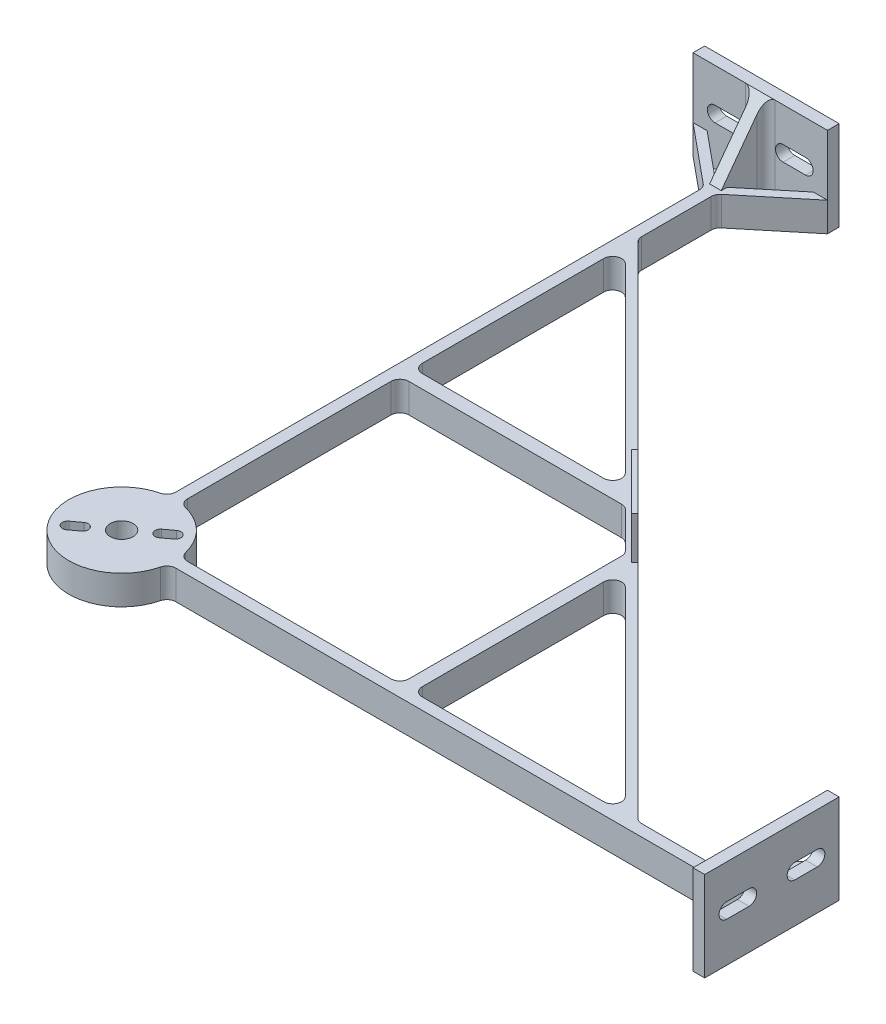
SolidWorks part; units mm, degrees
ref_plane "Front Plane" through (0, 0, 0) normal (0, 0, 1) x (1, 0, 0)
ref_plane "Top Plane" through (0, 0, 0) normal (0, 1, 0) x (1, 0, 0)
ref_plane "Right Plane" through (0, 0, 0) normal (1, 0, 0) x (0, 0, -1)
sketch "Sketch1" plane through (0, 0, 0) normal (0, 1, 0) x (1, 0, 0)
  line L0 (1.651, 14.8948) -> (1.651, 77.2021)
  line L1 (0, 0) -> (0, 189.2633) construction
  line L2 (-1.651, 14.8948) -> (-1.651, 180.975)
  line L3 (-1.651, 180.975) -> (1.651, 180.975)
  line L4 (-16.663, -12.33) -> (16.2408, 12.0176) construction
  line L5 (14.8948, -1.651) -> (180.975, -1.651)
  line L6 (6.3296, 4.6836) -> (8.7797, 6.4967) construction
  line L7 (5.4231, 5.9087) -> (7.8732, 7.7217)
  line L8 (180.975, -1.651) -> (180.975, 1.651)
  line L9 (14.8948, 1.651) -> (141.0789, 1.651)
  line L10 (7.2361, 3.4586) -> (9.6862, 5.2716)
  line L11 (0, 0) -> (12.0155, -16.238) construction
  line L12 (-6.3296, -4.6836) -> (-8.7797, -6.4967) construction
  line L13 (-7.2361, -3.4586) -> (-9.6862, -5.2716)
  line L14 (-5.4231, -5.9087) -> (-7.8732, -7.7217)
  line L15 (-1.651, 14.8948) -> (14.8948, -1.651) construction
  line L16 (1.651, 141.0789) -> (61.7178, 81.0121)
  line L17 (144.6711, 1.651) -> (1.651, 144.6711)
  line L18 (144.6711, 1.651) -> (166.629, 1.651)
  line L19 (141.0789, 1.651) -> (144.6711, 1.651) construction
  line L20 (1.651, 144.6711) -> (1.651, 180.975)
  line L21 (1.651, 81.0121) -> (61.7178, 81.0121)
  line L22 (1.651, 77.2021) -> (65.5278, 77.2021)
  line L23 (0, 0) -> (69.7604, 69.7604) construction
  line L24 (77.2021, 1.651) -> (77.2021, 65.5278)
  line L25 (81.0121, 1.651) -> (81.0121, 61.7178)
  line L26 (81.0121, 61.7178) -> (141.0789, 1.651)
  line L27 (65.5278, 77.2021) -> (77.2021, 65.5278)
  line L28 (1.651, 81.0121) -> (1.651, 141.0789)
  line L29 (169.921, 1.651) -> (180.975, 15.0573)
  line L30 (180.975, 15.0573) -> (180.975, 19.05)
  line L31 (180.975, 19.05) -> (166.629, 1.651)
  line L32 (166.4345, 0) -> (201.9953, 0) construction
  line L33 (180.975, -19.05) -> (166.629, -1.651)
  line L34 (180.975, -15.0573) -> (180.975, -19.05)
  line L35 (169.921, -1.651) -> (180.975, -15.0573)
  line L36 (169.921, 1.651) -> (180.975, 1.651)
  line L37 (166.629, 1.651) -> (169.921, 1.651) construction
  line L38 (-15.0573, 180.975) -> (-19.05, 180.975)
  line L39 (-19.05, 180.975) -> (-1.651, 166.629)
  line L40 (-1.651, 169.921) -> (-15.0573, 180.975)
  line L41 (1.651, 169.921) -> (15.0573, 180.975)
  line L42 (15.0573, 180.975) -> (19.05, 180.975)
  line L43 (19.05, 180.975) -> (1.651, 166.629)
  arc A0 (14.8948, 1.651) -> (1.651, 14.8948) centre (0, 0) ccw
  circle A1 centre (0, 0) radius 3.2385
  arc A2 (5.4231, 5.9087) -> (7.2361, 3.4586) centre (6.3296, 4.6836) ccw
  arc A3 (9.6862, 5.2716) -> (7.8732, 7.7217) centre (8.7797, 6.4967) ccw
  arc A4 (-7.2361, -3.4586) -> (-5.4231, -5.9087) centre (-6.3296, -4.6836) cw
  arc A5 (-7.8732, -7.7217) -> (-9.6862, -5.2716) centre (-8.7797, -6.4967) cw
  arc A6 (-1.651, 14.8948) -> (14.8948, -1.651) centre (0, 0) ccw
  point P14 (7.5546, 5.5901)
  point P25 (-7.5546, -5.5901)
  point P34 (142.875, 1.651)
  point P53 (168.275, 1.651)
  dimension "D3" = 29.972
  dimension "D1" = 6.477
  dimension "D6" = 1.524
  dimension "D7" = 3.048
  dimension "D2" = 53.5
  dimension "D4" = 3.302
  dimension "D5" = 3.302
  dimension "D8" = 7.874
  dimension "D9" = 2.54
  dimension "D10" = 38.1
  dimension "D11" = 3.81
  dimension "D12" = 16.51
  dimension "D13" = 38.1
  dimension "D14" = 12.7
  dimension "D15" = 2.54
  dimension "D16" = 180.975
  dimension "D17" = 180.975
extrude "Boss-Extrude1" add sketch "Sketch1" along normal blind 8.255 contours L2 A6 L5 L8 L36 L29 L30 L31 L18 L17 L20 L3 L14 A5 L13 A4 L9 A0 L0 L22 L27 L24 L25 L26 L21 L28 L16 A1 A3 L10 A2 L7 | L35 L5 L33 L34 | L2 L40 L38 L39 | L43 L42 L41 L20 region at (1.1203, 0, -90.7619) region at (-9.3955, 0, -174.5894) region at (174.5894, 0, 9.3955) region at (9.3955, 0, -174.5894)
sketch "Sketch3" plane through (0, 0, 0) normal (0, 1, 0) x (1, 0, 0)
  line L0 (0, 0) -> (128.7769, 128.7769) construction
  line L1 (180.975, 19.05) -> (184.277, 19.05)
  line L2 (180.975, 19.05) -> (180.975, -19.05)
  line L3 (180.975, -19.05) -> (184.277, -19.05)
  line L4 (184.277, 19.05) -> (184.277, -19.05)
  line L5 (19.05, 184.277) -> (-19.05, 184.277)
  line L6 (-19.05, 180.975) -> (-19.05, 184.277)
  line L7 (19.05, 180.975) -> (-19.05, 180.975)
  line L8 (19.05, 180.975) -> (19.05, 184.277)
  dimension "D1" = 3.302
extrude "Boss-Extrude3" add sketch "Sketch3" along normal blind 25.4
sketch "Sketch4" plane through (0, 8.255, 0) normal (0, 1, 0) x (1, 0, 0)
  line L0 (65.2584, 81.0637) -> (64.3604, 80.1656)
  line L1 (144.6711, 1.651) -> (1.651, 144.6711) construction
  line L2 (64.3604, 80.1656) -> (80.1656, 64.3604)
  line L3 (80.1656, 64.3604) -> (81.0637, 65.2584)
  line L4 (81.0637, 65.2584) -> (65.2584, 81.0637)
  line L5 (71.365, 71.365) -> (72.263, 72.263) construction
  line L6 (65.5278, 77.2021) -> (77.2021, 65.5278) construction
  dimension "D1" = 22.352
  dimension "D2" = 1.27
extrude "Boss-Extrude4" add sketch "Sketch4" along normal blind 11.938
sketch "Sketch5" plane through (184.277, 0, 0) normal (1, 0, 0) x (0, 0, -1)
  line L0 (-12.827, 13.4726) -> (-6.477, 13.4726) construction
  line L1 (-12.827, 15.6316) -> (-6.477, 15.6316)
  line L2 (-12.827, 11.3136) -> (-6.477, 11.3136)
  line L3 (0, 4.9298) -> (0, 30.0782) construction
  line L4 (12.827, 13.4726) -> (6.477, 13.4726) construction
  line L5 (12.827, 15.6316) -> (6.477, 15.6316)
  line L6 (12.827, 11.3136) -> (6.477, 11.3136)
  arc A0 (-12.827, 15.6316) -> (-12.827, 11.3136) centre (-12.827, 13.4726) ccw
  arc A1 (-6.477, 11.3136) -> (-6.477, 15.6316) centre (-6.477, 13.4726) ccw
  arc A2 (12.827, 15.6316) -> (12.827, 11.3136) centre (12.827, 13.4726) cw
  arc A3 (6.477, 11.3136) -> (6.477, 15.6316) centre (6.477, 13.4726) cw
  point P2 (-9.652, 13.4726)
  point P12 (9.652, 13.4726)
  dimension "D1" = 6.35
  dimension "D2" = 4.318
  dimension "D3" = 9.652
ref_plane "Plane1" through (0, 0, 0) normal (0.7071, 0, 0.7071) x (0.7071, 0, -0.7071)
extrude "Cut-Extrude1" cut sketch "Sketch5" against normal through all
mirror "Mirror1" about plane through (0, 0, 0) normal (0.7071, 0, 0.7071) of "Cut-Extrude1"
sketch "Sketch6" plane through (0, 0, 0) normal (0, 1, 0) x (1, 0, 0)
  line L0 (169.921, 1.651) -> (180.975, 1.651) construction
  line L1 (180.975, -1.651) -> (168.275, -1.651)
  line L2 (180.975, -1.651) -> (180.975, 1.651)
  line L3 (180.975, 1.651) -> (168.275, 1.651)
  line L4 (168.275, -1.651) -> (168.275, 1.651)
  dimension "D1" = 12.7
extrude "Boss-Extrude5" add sketch "Sketch6" along normal blind 25.4
sketch "Sketch7" plane through (0, 0, -1.651) normal (0, 0, -1) x (-1, 0, 0)
  line L0 (-180.975, 25.4) -> (-168.275, 8.255)
  line L1 (-168.275, 8.255) -> (-168.275, 25.4)
  line L2 (-168.275, 25.4) -> (-180.975, 25.4)
extrude "Cut-Extrude2" cut sketch "Sketch7" against normal blind 25.4
sketch "Sketch8" plane through (0, 0, 0) normal (0, 1, 0) x (1, 0, 0)
  line L0 (1.651, 169.921) -> (1.651, 180.975) construction
  line L1 (-1.651, 180.975) -> (1.651, 180.975)
  line L2 (-1.651, 180.975) -> (-1.651, 168.275)
  line L3 (-1.651, 168.275) -> (1.651, 168.275)
  line L4 (1.651, 180.975) -> (1.651, 168.275)
  dimension "D1" = 12.7
extrude "Boss-Extrude6" add sketch "Sketch8" along normal blind 25.4
sketch "Sketch9" plane through (1.651, 0, 0) normal (1, 0, 0) x (0, 0, -1)
  line L0 (180.975, 25.4) -> (168.275, 8.255)
  line L1 (168.275, 8.255) -> (168.275, 25.4)
  line L2 (168.275, 25.4) -> (180.975, 25.4)
extrude "Cut-Extrude3" cut sketch "Sketch9" against normal blind 25.4
fillet "Fillet1" radius 2.54 24 edges at (180.975, 12.7, 1.651) (-1.651, 12.7, -180.975) (141.0789, 4.1275, -1.651) (61.7178, 4.1275, -81.0121) (1.651, 4.1275, -141.0789) (81.0121, 4.1275, -61.7178) (14.8948, 4.1275, 1.651) (-1.651, 4.1275, -14.8948) (180.975, 12.7, -1.651) (77.2021, 4.1275, -1.651) (1.651, 12.7, -180.975) (1.651, 4.1275, -77.2021) (166.629, 4.1275, 1.651) (65.5278, 4.1275, -77.2021) (-1.651, 4.1275, -166.629) (77.2021, 4.1275, -65.5278) (1.651, 4.1275, -166.629) (1.651, 4.1275, -14.8948) (1.651, 4.1275, -144.6711) (1.651, 4.1275, -81.0121) (81.0121, 4.1275, -1.651) (166.629, 4.1275, -1.651) (14.8948, 4.1275, -1.651) (144.6711, 4.1275, -1.651)
